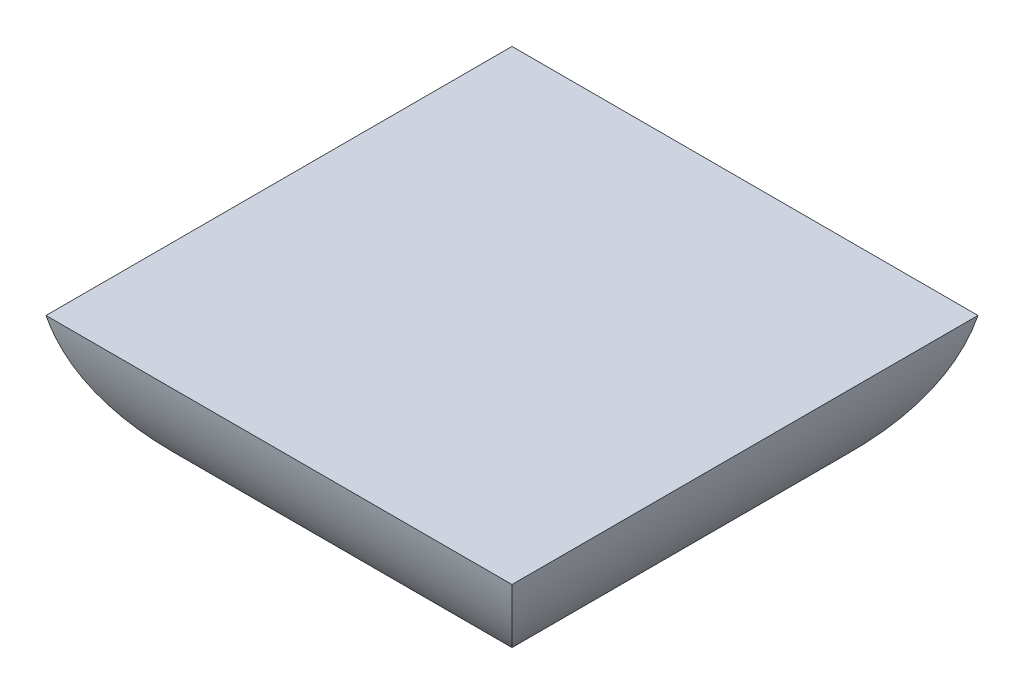
SolidWorks part; units mm, degrees
ref_plane "Front Plane" through (0, 0, 0) normal (0, 0, 1) x (1, 0, 0)
ref_plane "Top Plane" through (0, 0, 0) normal (0, 1, 0) x (1, 0, 0)
ref_plane "Right Plane" through (0, 0, 0) normal (1, 0, 0) x (0, 0, -1)
sketch "Sketch1" plane through (0, 0, 0) normal (0, 0, 1) x (1, 0, 0)
  line L1 (-12.7, -5.08) -> (12.7, -5.08)
  line L2 (-12.7, -5.08) -> (-12.7, 5.08)
  line L3 (-12.7, 5.08) -> (12.7, 5.08)
  line L4 (12.7, -5.08) -> (12.7, 5.08)
  line L5 (-12.7, -5.08) -> (12.7, 5.08) construction
  line L6 (-12.7, 5.08) -> (12.7, -5.08) construction
  point P0 (0, 0)
  dimension "D1" = 25.4
  dimension "D2" = 10.16
extrude "Boss-Extrude1" add sketch "Sketch1" along normal blind 25.4
fillet "Fillet1" radius 12.7 4 edges at (-12.7, -5.08, 12.7) (0, -5.08, 25.4) (12.7, -5.08, 12.7) (0, -5.08, 0)
